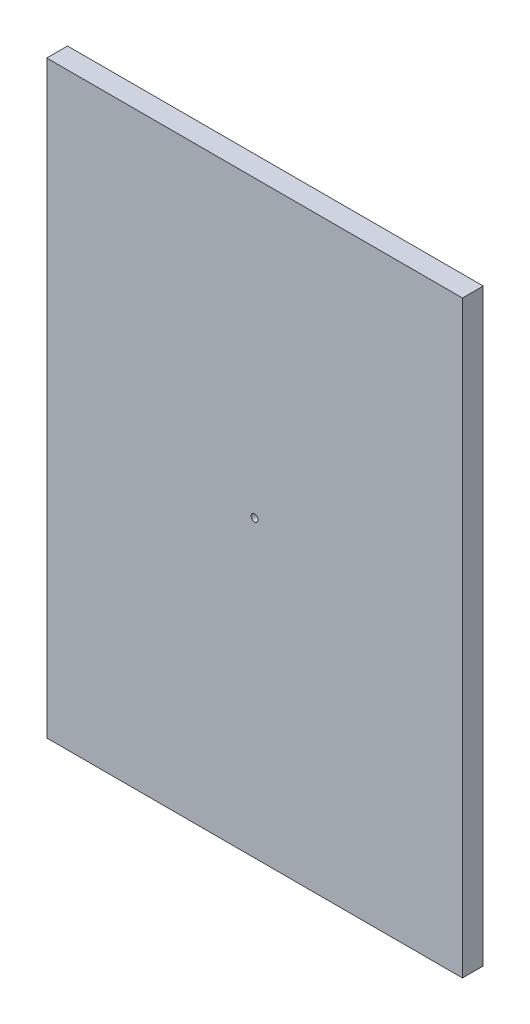
SolidWorks part; units mm, degrees
material "Glass"
ref_plane "Front Plane" through (0, 0, 0) normal (0, 0, 1) x (1, 0, 0)
ref_plane "Top Plane" through (0, 0, 0) normal (0, 1, 0) x (1, 0, 0)
ref_plane "Right Plane" through (0, 0, 0) normal (1, 0, 0) x (0, 0, -1)
sketch "Sketch1" plane through (0, 0, 0) normal (0, 0, 1) x (1, 0, 0)
  line L1 (0, 0) -> (60, 0)
  line L2 (0, 0) -> (0, -85)
  line L3 (0, -85) -> (60, -85)
  line L4 (60, 0) -> (60, -85)
  circle A0 centre (30, -42.5) radius 0.5
  point P7 (60, -42.5)
  point P8 (30, 0)
  dimension "D3" = 1
  dimension "D1" = 60
  dimension "D2" = 85
extrude "Boss-Extrude1" add sketch "Sketch1" along normal blind 3 contours L4 L1 L2 L3 A0 region at (30, -1.0404, 0)
ref_plane "Plane1" through (30, 0, 0) normal (1, 0, 0) x (0, 0, -1)
sketch "Sketch2" plane through (30, 0, 0) normal (1, 0, 0) x (0, 0, -1)
  line L1 (-3, -42.5) -> (-8, -42.5) construction
  line L2 (-3, -42.5) -> (-215.132, 169.632) construction
  line L4 (-3, 0) -> (-3, -85) construction
  point P0 (-3, -42.3413)
  dimension "D1" = 5
  dimension "D2" = 45
  dimension "D4" = 300
